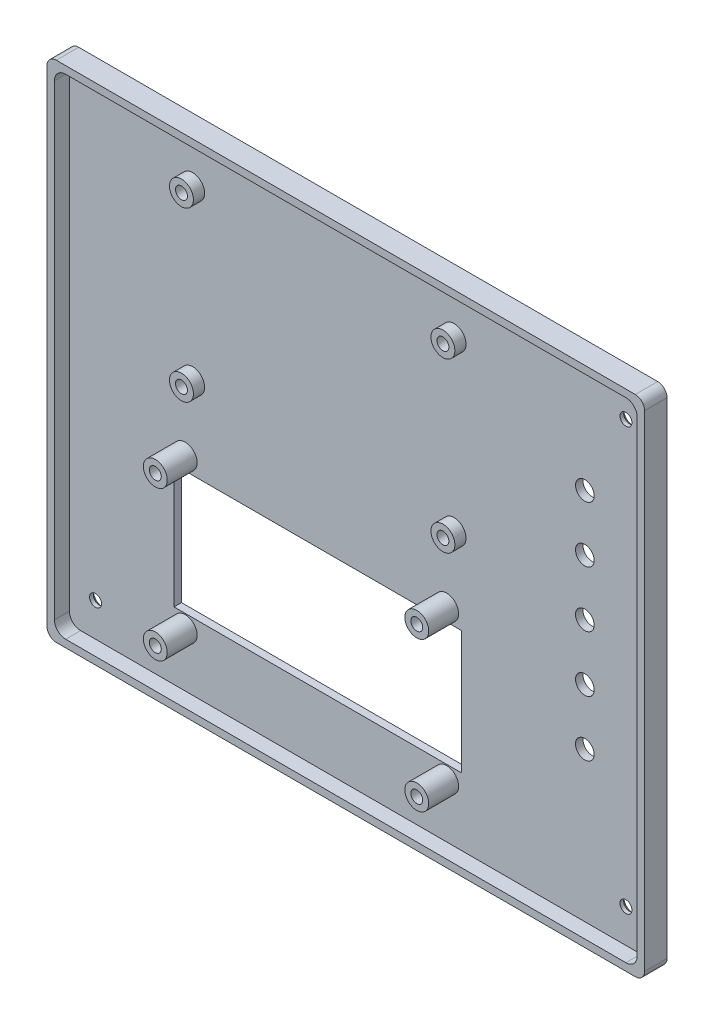
SolidWorks part; units mm, degrees
note: The reader was unsure of these and kept them because the rebuilt part matched: shared geometry of "Esquisse1<10>", "Esquisse1<11>", "Esquisse2<14>", "Esquisse6<6>", "Esquisse2<16>", "Esquisse2<17>".
ref_plane "Plan de face" through (0, 0, 0) normal (0, 0, 1) x (1, 0, 0)
ref_plane "Plan de dessus" through (0, 0, 0) normal (0, 1, 0) x (1, 0, 0)
ref_plane "Plan de droite" through (0, 0, 0) normal (1, 0, 0) x (0, 0, -1)
sketch "Esquisse1" plane through (0, 0, 0) normal (0, 0, 1) x (1, 0, 0)
  line L0 (0, 75.8757) -> (160, 75.8757) construction
  line L5 (5, 13.3757) -> (13, 25.3757) construction
  line L10 (2.5, 10.8757) -> (157.5, 140.8757) construction
  line L11 (2.5, 140.8757) -> (157.5, 10.8757) construction
  line L12 (5, 13.3757) -> (155, 13.3757)
  line L13 (5, 13.3757) -> (5, 138.3757)
  line L14 (5, 138.3757) -> (155, 138.3757)
  line L15 (155, 13.3757) -> (155, 138.3757)
  line L16 (5, 13.3757) -> (155, 138.3757) construction
  line L17 (5, 138.3757) -> (155, 13.3757) construction
  line L20 (155, 126.3757) -> (147, 126.3757)
  line L21 (147, 138.3757) -> (147, 126.3757)
  line L28 (155, 25.3757) -> (147, 25.3757)
  line L29 (147, 13.3757) -> (147, 25.3757)
  line L31 (155, 138.3757) -> (147, 126.3757) construction
  line L32 (147, 138.3757) -> (155, 126.3757) construction
  line L33 (155, 25.3757) -> (147, 13.3757) construction
  line L34 (147, 25.3757) -> (155, 13.3757) construction
  line L35 (5, 141.3757) -> (155, 141.3757)
  line L36 (158, 138.3757) -> (158, 13.3757)
  line L37 (155, 10.3757) -> (5, 10.3757)
  line L38 (2, 13.3757) -> (2, 138.3757)
  line L39 (160, 10.8757) -> (160, 140.8757)
  line L40 (157.5, 143.3757) -> (2.5, 143.3757)
  line L41 (0, 140.8757) -> (0, 10.8757)
  line L42 (2.5, 8.3757) -> (157.5, 8.3757)
  line L44 (5, 25.3757) -> (13, 25.3757)
  line L45 (13, 13.3757) -> (13, 25.3757)
  line L46 (5, 25.3757) -> (13, 13.3757) construction
  arc A1 (157.5, 143.3757) -> (160, 140.8757) centre (157.5, 140.8757) cw
  arc A3 (0, 140.8757) -> (2.5, 143.3757) centre (2.5, 140.8757) cw
  arc A5 (0, 10.8757) -> (2.5, 8.3757) centre (2.5, 10.8757) ccw
  arc A7 (160, 10.8757) -> (157.5, 8.3757) centre (157.5, 10.8757) cw
  circle A8 centre (151, 19.3757) radius 1.6
  circle A9 centre (151, 132.3757) radius 1.6
  circle A10 centre (9, 19.3757) radius 1.6
  arc A11 (158, 13.3757) -> (155, 10.3757) centre (155, 13.3757) cw
  arc A12 (155, 141.3757) -> (158, 138.3757) centre (155, 138.3757) cw
  arc A13 (5, 141.3757) -> (2, 138.3757) centre (5, 138.3757) ccw
  arc A14 (2, 13.3757) -> (5, 10.3757) centre (5, 13.3757) ccw
  circle A15 centre (140, 110.3757) radius 2.5
  circle A16 centre (140, 95.3757) radius 2.5
  circle A17 centre (140, 80.3757) radius 2.5
  circle A18 centre (140, 65.3757) radius 2.5
  circle A19 centre (140, 50.3757) radius 2.5
  point P7 (80, 75.8757)
  point P12 (80, 75.8757)
  dimension "D13" = 135
  dimension "D20" = 11
  dimension "D2" = 17
  dimension "D3" = 130
  dimension "D4" = 155
  dimension "D5" = 150
  dimension "D6" = 125
  dimension "D7" = 13
  dimension "D8" = 17
  dimension "D9" = 13
  dimension "D10" = 160
  dimension "D11" = 13
  dimension "D12" = 17
  dimension "D14" = 113
  dimension "D15" = 142
  dimension "D17" = 3
  dimension "D18" = 3
  dimension "D21" = 22
  dimension "D22" = 15
  dimension "D23" = 11
  dimension "D24" = 15
  dimension "D25" = 11
  dimension "D26" = 15
  dimension "D27" = 11
  dimension "D28" = 15
  dimension "D29" = 11
extrude "Boss.-Extru.4" add sketch "Esquisse1" along normal blind 2
extrude "Boss.-Extru.5" add sketch "Esquisse1<10>" along normal blind 6
sketch "Esquisse1<10>" plane through (0, 0, 0) normal (0, 0, 1) x (1, 0, 0) same geometry as "Esquisse1"
sketch "Esquisse7" plane through (0, 0, 0) normal (0, 0, -1) x (-1, 0, 0)
  line L0 (-157.5, 143.3757) -> (-2.5, 143.3757) construction
  line L1 (0, 140.8757) -> (0, 10.8757) construction
  circle A0 centre (-35, 83.3757) radius 1.6
  circle A1 centre (-35, 83.3757) radius 3.2
  circle A2 centre (-35, 128.3757) radius 1.6
  circle A3 centre (-35, 128.3757) radius 3.2
  circle A4 centre (-105, 83.3757) radius 1.6
  circle A5 centre (-105, 83.3757) radius 3.2
  circle A6 centre (-105, 128.3757) radius 1.6
  circle A7 centre (-105, 128.3757) radius 3.2
  dimension "D1" = 45
  dimension "D2" = 70
  dimension "D3" = 45
  dimension "D4" = 70
  dimension "D5" = 15
  dimension "D6" = 35
extrude "Enlèv. mat.-Extru.2" cut sketch "Esquisse1<11>" along normal blind 17 contours A9
sketch "Esquisse1<11>" plane through (0, 0, 0) normal (0, 0, 1) x (1, 0, 0) same geometry as "Esquisse1"
sketch "Esquisse2" plane through (0, 0, 2) normal (0, 0, 1) x (1, 0, 0)
  line L0 (217.199, 407.0545) -> (625.199, 407.0545) construction
  line L1 (143.6962, 186.4251) -> (293.0295, 186.4251) construction
  line L2 (81.3885, -140.3646) -> (-326.6115, -140.3646) construction
  line L3 (61.6054, -160.51) -> (-346.3946, -160.51) construction
  line L4 (128.0952, 53.263) -> (121.7387, 47.1058) construction
  line L5 (128.0952, 53.263) -> (134.4535, 47.1058) construction
  line L6 (128.0927, 76.3532) -> (128.0927, 8.3757) construction
  line L7 (2.5, 8.3757) -> (157.5, 8.3757) construction
  line L8 (98.4923, -8.9067) -> (-50.841, -8.9067) construction
  line L9 (43.5812, -200.0519) -> (-533.7521, -200.0519) construction
  line L11 (110.0271, 293.9591) -> (-231.3062, 293.9591) construction
  line L15 (123.3038, 79.8702) -> (123.3038, 85.2793)
  line L17 (132.8739, 79.8702) -> (132.8739, 85.2793)
  line L18 (131.6131, 86.5401) -> (124.5646, 86.5401)
  line L19 (130.4916, 76.6088) -> (130.4916, 78.7466)
  line L20 (15.7517, -184.5424) -> (-470.2483, -184.5424) construction
  line L21 (130.4916, 78.7466) -> (125.7221, 78.7466)
  line L22 (120.9839, 92.0968) -> (120.9839, 93.6375)
  line L23 (120.9839, 97.43) -> (120.9839, 98.9534)
  line L24 (128.0927, 8.3757) -> (128.0927, 143.3757) construction
  line L25 (77.5725, -104.5063) -> (-162.4275, -104.5063) construction
  line L26 (119.4747, 96.82) -> (119.4747, 94.2474)
  line L28 (120.0847, 93.6375) -> (120.9839, 93.6375)
  line L29 (120.0847, 97.43) -> (120.9839, 97.43)
  line L30 (121.5939, 99.5634) -> (134.5596, 99.5634)
  line L31 (135.1695, 98.9534) -> (135.1695, 92.0968)
  line L32 (134.5596, 91.4869) -> (121.5939, 91.4869)
  line L33 (133.9512, 98.3427) -> (133.9512, 92.707)
  line L34 (133.9512, 92.707) -> (122.2045, 92.707)
  line L35 (122.2045, 98.3427) -> (122.2045, 92.707)
  line L36 (122.2045, 98.3427) -> (133.9512, 98.3427)
  line L37 (132.259, 75.8158) -> (132.259, 78.8684)
  line L38 (123.8951, 76.1896) -> (123.8951, 78.8807)
  line L39 (125.7221, 75.886) -> (125.7221, 78.7466)
  line L40 (-152.8212, -141.8547) -> (-638.8212, -141.8547) construction
  line L41 (128.1205, 114.3764) -> (135.9178, 106.5214)
  line L42 (133.6575, 104.528) -> (127.1026, 111.1314)
  line L43 (124.1677, 108.2226) -> (127.1026, 111.1314)
  line L44 (121.9674, 110.288) -> (126.0474, 114.3267)
  line L45 (127.2733, -55.2164) -> (-358.7267, -55.2164) construction
  line L46 (157.5, 143.3757) -> (2.5, 143.3757) construction
  line L47 (125.0525, 255.6387) -> (519.0525, 255.6387) construction
  line L48 (0, 140.8757) -> (0, 10.8757) construction
  circle A3 centre (128.0952, 53.263) radius 1.4253
  circle A16 centre (128.0576, 68.7162) radius 0.9491
  circle A17 centre (131.4234, 67.2558) radius 1.1971
  circle A20 centre (132.8725, 63.8771) radius 1.4512
  circle A21 centre (131.4234, 60.48) radius 1.5323
  circle A25 centre (123.1751, 63.8771) radius 0.5249
  arc A28 (130.1783, 51.2458) -> (126.0124, 51.2455) centre (128.0952, 53.263) cw
  arc A29 (131.2654, 50.1931) -> (124.9255, 50.1927) centre (128.0952, 53.263) cw
  arc A30 (132.0462, 49.437) -> (124.1448, 49.4365) centre (128.0952, 53.263) cw
  arc A31 (133.3052, 48.2178) -> (122.886, 48.2171) centre (128.0952, 53.263) cw
  arc A32 (133.9099, 47.6321) -> (122.2813, 47.6314) centre (128.0952, 53.263) cw
  arc A33 (134.9655, 46.5487) -> (121.1952, 46.5793) centre (128.0952, 53.263) cw
  circle A34 centre (124.6029, 67.2558) radius 0.7142
  circle A35 centre (128.0576, 59.0055) radius 1.8599
  arc A51 (126.0124, 51.2455) -> (124.9255, 50.1927) centre (125.469, 50.7191) ccw
  arc A53 (124.1448, 49.4365) -> (122.886, 48.2171) centre (123.5154, 48.8268) ccw
  arc A55 (130.1783, 51.2458) -> (131.2654, 50.1931) centre (130.7219, 50.7194) cw
  arc A56 (132.0462, 49.437) -> (133.3052, 48.2178) centre (132.6757, 48.8274) cw
  arc A57 (133.9099, 47.6321) -> (134.9655, 46.5487) centre (134.4535, 47.1058) cw
  arc A58 (122.2813, 47.6314) -> (121.1952, 46.5793) centre (121.7382, 47.1054) ccw
  arc A70 (123.3038, 85.2793) -> (124.5646, 86.5401) centre (124.5646, 85.2793) cw
  arc A71 (131.6131, 86.5401) -> (132.8739, 85.2793) centre (131.6131, 85.2793) cw
  arc A72 (132.259, 75.8158) -> (123.8951, 76.1896) centre (128.0927, 76.3532) cw
  arc A73 (130.4916, 76.6088) -> (125.7221, 75.886) centre (128.0886, 76.368) cw
  arc A79 (132.8739, 79.8702) -> (132.259, 78.8684) centre (131.7503, 79.8702) cw
  arc A80 (123.3038, 79.8702) -> (123.8951, 78.8807) centre (124.4274, 79.8702) ccw
  arc A81 (135.9178, 106.5214) -> (133.6575, 104.528) centre (134.8465, 105.4579) cw
  arc A82 (121.9674, 110.288) -> (124.1677, 108.2226) centre (123.0297, 109.2149) ccw
  arc A83 (128.1205, 114.3764) -> (126.0474, 114.3267) centre (127.1075, 113.3708) ccw
  arc A84 (134.5596, 91.4869) -> (135.1695, 92.0968) centre (134.5596, 92.0968) ccw
  arc A85 (121.5939, 91.4869) -> (120.9839, 92.0968) centre (121.5939, 92.0968) cw
  arc A86 (120.9839, 98.9534) -> (121.5939, 99.5634) centre (121.5939, 98.9534) cw
  arc A87 (134.5596, 99.5634) -> (135.1695, 98.9534) centre (134.5596, 98.9534) cw
  arc A88 (120.0847, 93.6375) -> (119.4747, 94.2474) centre (120.0847, 94.2474) cw
  arc A89 (119.4747, 96.82) -> (120.0847, 97.43) centre (120.0847, 96.82) cw
  circle A90 centre (68, 100.8027) radius 8.5845
  arc A91 (80.5204, 113.3709) -> (80.5681, 88.2823) centre (68, 100.8027) cw
  arc A92 (83.5289, 116.1618) -> (83.3591, 85.2739) centre (68, 100.8027) cw
  arc A93 (89.6704, 119.6503) -> (89.4241, 81.6756) centre (68, 100.8027) cw
  arc A94 (92.7901, 122.3636) -> (92.462, 78.8702) centre (68, 100.8027) cw
  arc A95 (98.4098, 126.7207) -> (98.7199, 75.2532) centre (68, 100.8027) cw
  arc A96 (101.4652, 129.3247) -> (101.6745, 72.5281) centre (68, 100.8027) cw
  arc A97 (55.5527, 113.3709) -> (55.4319, 88.3554) centre (68, 100.8027) ccw
  arc A98 (52.6279, 116.1618) -> (52.6409, 85.4306) centre (68, 100.8027) ccw
  arc A99 (46.273, 119.6504) -> (46.3713, 81.8423) centre (68, 100.8027) ccw
  arc A100 (43.1453, 122.3636) -> (43.2578, 79.1129) centre (68, 100.8027) ccw
  arc A101 (37.6873, 126.6944) -> (37.4563, 75.1839) centre (68, 100.8027) ccw
  arc A102 (34.5771, 129.351) -> (34.3225, 72.5553) centre (68, 100.8027) ccw
  arc A104 (37.4563, 75.1839) -> (34.3225, 72.5553) centre (35.8894, 73.8696) cw
  arc A105 (34.5771, 129.351) -> (37.6873, 126.6944) centre (36.1322, 128.0227) cw
  arc A106 (43.1453, 122.3636) -> (46.273, 119.6504) centre (44.7091, 121.007) cw
  arc A107 (46.3713, 81.8423) -> (43.2578, 79.1129) centre (44.8146, 80.4776) cw
  arc A108 (55.4319, 88.3554) -> (52.6409, 85.4306) centre (54.0364, 86.893) cw
  arc A109 (52.6279, 116.1618) -> (55.5527, 113.3709) centre (54.0903, 114.7663) cw
  arc A110 (80.5204, 113.3709) -> (83.5289, 116.1618) centre (82.0246, 114.7663) cw
  arc A111 (83.3591, 85.2739) -> (80.5681, 88.2823) centre (81.9636, 86.7781) cw
  arc A112 (92.462, 78.8702) -> (89.4241, 81.6756) centre (90.9431, 80.2729) cw
  arc A113 (89.6704, 119.6503) -> (92.7901, 122.3636) centre (91.2303, 121.007) cw
  arc A114 (98.4098, 126.7207) -> (101.4652, 129.3247) centre (99.9375, 128.0227) cw
  arc A115 (101.6745, 72.5281) -> (98.7199, 75.2532) centre (100.1972, 73.8906) cw
  dimension "D1" = 68
extrude "Enlèv. mat.-Extru.4" cut sketch "Esquisse2" against normal blind 11 contours A3 | A55 A28 A51 A29 | A32 A58 A33 A57 | A34 | A25 | A16 | A17 | A20 | A21 | A35 | A30 A53 A31 A56 | A80 L38 A72 L37 A79 L17 A71 L18 A70 L15 | L21 L39 A73 L19 | L23 A86 L30 A87 L31 A84 L32 A85 L22 L28 A88 L26 A89 L29 | L34 L35 L36 L33 | L42 L43 A82 L44 A83 L41 A81 | A90 | A111 A91 A110 A92 | A113 A94 A112 A93 | A115 A95 A114 A96 | A109 A97 A108 A98 | A107 A100 A106 A99 | A105 A101 A104 A102
extrude "Boss.-Extru.9" add sketch "Esquisse2<14>" against normal blind 1
sketch "Esquisse2<14>" plane through (0, 0, 2) normal (0, 0, 1) x (1, 0, 0) same geometry as "Esquisse2"
sketch "Esquisse6" plane through (0, 0, 0) normal (0, 0, -1) x (-1, 0, 0)
  line L0 (-2.5, 8.3757) -> (-157.5, 8.3757) construction
  line L1 (-107, 61.3757) -> (-30, 61.3757)
  line L2 (-107, 61.3757) -> (-107, 28.3757)
  line L3 (-107, 28.3757) -> (-30, 28.3757)
  line L4 (-30, 61.3757) -> (-30, 28.3757)
  line L5 (0, 140.8757) -> (0, 10.8757) construction
  circle A0 centre (-33, 64.8757) radius 1.6
  circle A1 centre (-33, 24.8757) radius 1.6
  circle A2 centre (-103, 64.8757) radius 1.6
  circle A3 centre (-103, 24.8757) radius 1.6
  circle A4 centre (-103, 64.8757) radius 3.2
  circle A5 centre (-103, 24.8757) radius 3.2
  circle A6 centre (-33, 24.8757) radius 3.2
  circle A7 centre (-33, 64.8757) radius 3.2
  point P19 (-103.535, 24.8757)
  point P21 (-33, 24.728)
  point P23 (-33, 65.0534)
  point P26 (-39.1407, 89.4866)
  point P27 (-42.9192, 92.0181)
  point P31 (-42.9192, 119.6477)
  point P35 (-92.2577, 92.0181)
  point P39 (-92.2577, 119.6477)
  point P40 (0, 0)
  point P41 (0, 0)
  point P42 (0, 0)
  dimension "D5" = 40
  dimension "D6" = 70
  dimension "D1" = 77
  dimension "D2" = 33
  dimension "D3" = 20
  dimension "D4" = 30
  dimension "D7" = 40
  dimension "D8" = 70
  dimension "D9" = 4
  dimension "D10" = 3.5
  dimension "D11" = 3.5
extrude "Boss.-Extru.10" add sketch "Esquisse6" against normal blind 10
chamfer "Chanfrein3" distance 1 3 edges at (152.6, 19.3757, 0) (10.6, 19.3757, 0) (152.6, 132.3757, 0)
extrude "Enlèv. mat.-Extru.5" cut sketch "Esquisse6<6>" against normal blind 10 contours L4 L1 L2 L3
sketch "Esquisse6<6>" plane through (0, 0, 0) normal (0, 0, -1) x (-1, 0, 0) same geometry as "Esquisse6"
extrude "Boss.-Extru.11" add sketch "Esquisse7" against normal blind 5
extrude "Enlèv. mat.-Extru.7" cut sketch "Esquisse2<16>" against normal blind 3
sketch "Esquisse2<16>" plane through (0, 0, 2) normal (0, 0, 1) x (1, 0, 0) same geometry as "Esquisse2"
extrude "Boss.-Extru.12" add sketch "Esquisse2<17>" against normal blind 1
sketch "Esquisse2<17>" plane through (0, 0, 2) normal (0, 0, 1) x (1, 0, 0) same geometry as "Esquisse2"
